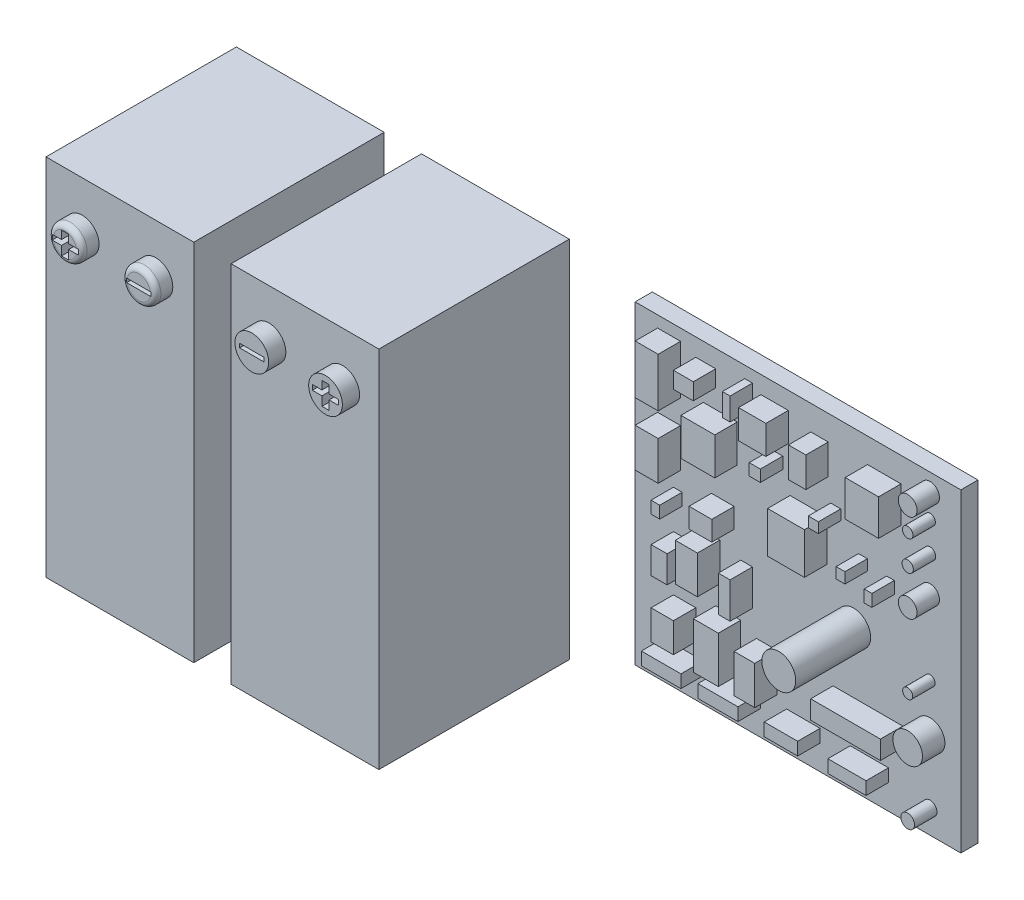
SolidWorks part; units mm, degrees
ref_plane "Front Plane" through (0, 0, 0) normal (0, 0, 1) x (1, 0, 0)
ref_plane "Top Plane" through (0, 0, 0) normal (0, 1, 0) x (1, 0, 0)
ref_plane "Right Plane" through (0, 0, 0) normal (1, 0, 0) x (0, 0, -1)
sketch "Sketch1" plane through (0, 0, 0) normal (0, 0, 1) x (1, 0, 0)
  line L0 (0, 0) -> (-440.234, 0) construction
  line L1 (-308.8617, 138.7667) -> (-252.5588, 138.7667)
  line L2 (-308.8617, 138.7667) -> (-308.8617, 0)
  line L3 (-308.8617, 0) -> (-252.5588, 0)
  line L4 (-252.5588, 138.7667) -> (-252.5588, 0)
  line L5 (-238.3409, 138.7667) -> (-182.0381, 138.7667)
  line L6 (-238.3409, 138.7667) -> (-238.3409, 0)
  line L7 (-238.3409, 0) -> (-182.0381, 0)
  line L8 (-182.0381, 138.7667) -> (-182.0381, 0)
  dimension "D1" = 182.0381
  dimension "D2" = 238.3409
  dimension "D3" = 252.5588
  dimension "D4" = 138.7667
extrude "Boss-Extrude1" add sketch "Sketch1" along normal blind 72.54
sketch "Sketch2" plane through (0, 0, 72.54) normal (0, 0, 1) x (1, 0, 0)
  line L1 (-296.4204, 124.1037) -> (-293.7159, 124.1037)
  line L2 (-296.4204, 124.1037) -> (-296.4204, 120.9679)
  line L3 (-296.4204, 115.561) -> (-293.7159, 115.561)
  line L4 (-293.7159, 124.1037) -> (-293.7159, 120.9679)
  line L5 (-299.9672, 120.9679) -> (-296.4204, 120.9679)
  line L6 (-299.9672, 120.9679) -> (-299.9672, 119.0321)
  line L7 (-299.9672, 119.0321) -> (-296.4204, 119.0321)
  line L8 (-290.0552, 120.9679) -> (-290.0552, 119.0321)
  line L9 (-271.5851, 120.6951) -> (-262.3839, 120.6951)
  line L10 (-271.5851, 120.6951) -> (-271.5851, 119.1782)
  line L11 (-271.5851, 119.1782) -> (-262.3839, 119.1782)
  line L12 (-262.3839, 120.6951) -> (-262.3839, 119.1782)
  line L28 (-293.7159, 119.0321) -> (-290.0552, 119.0321)
  line L29 (-296.4204, 119.0321) -> (-296.4204, 115.561)
  line L30 (-293.7159, 120.9679) -> (-290.0552, 120.9679)
  line L31 (-293.7159, 119.0321) -> (-293.7159, 115.561)
  line L32 (75.3138, 0) -> (-389.5943, 0) construction
  line L33 (-373.4137, 120) -> (67.9111, 120) construction
  line L34 (-308.8617, 138.7667) -> (-308.8617, 0) construction
  line L35 (-295.0748, 110.7152) -> (-295.0748, 129.2848) construction
  line L36 (-308.8617, 0) -> (-252.5588, 0) construction
  line L37 (-304.6062, 120) -> (-285.5434, 120) construction
  line L38 (-266.9845, 132.8771) -> (-266.9845, 104.478) construction
  line L40 (-238.3409, 138.7667) -> (-252.5588, 138.7667) construction
  line L42 (-245.4499, 138.7667) -> (-245.4499, -65.5199) construction
  line L43 (-223.9153, 132.8771) -> (-223.9153, 104.478) construction
  line L44 (-186.2936, 120) -> (-205.3564, 120) construction
  line L45 (-195.825, 110.7152) -> (-195.825, 129.2848) construction
  line L46 (-117.486, 120) -> (-558.8109, 120) construction
  line L47 (-197.1839, 119.0321) -> (-197.1839, 115.561)
  line L48 (-197.1839, 120.9679) -> (-200.8445, 120.9679)
  line L49 (-194.4793, 119.0321) -> (-194.4793, 115.561)
  line L50 (-197.1839, 119.0321) -> (-200.8445, 119.0321)
  line L51 (-228.5159, 120.6951) -> (-228.5159, 119.1782)
  line L52 (-219.3147, 119.1782) -> (-228.5159, 119.1782)
  line L53 (-219.3147, 120.6951) -> (-219.3147, 119.1782)
  line L54 (-219.3147, 120.6951) -> (-228.5159, 120.6951)
  line L55 (-200.8445, 120.9679) -> (-200.8445, 119.0321)
  line L56 (-190.9326, 119.0321) -> (-194.4793, 119.0321)
  line L57 (-190.9326, 120.9679) -> (-190.9326, 119.0321)
  line L58 (-190.9326, 120.9679) -> (-194.4793, 120.9679)
  line L59 (-197.1839, 124.1037) -> (-197.1839, 120.9679)
  line L60 (-194.4793, 115.561) -> (-197.1839, 115.561)
  line L61 (-194.4793, 124.1037) -> (-194.4793, 120.9679)
  line L62 (-194.4793, 124.1037) -> (-197.1839, 124.1037)
  circle A0 centre (-295.0748, 120) radius 6.4293
  circle A1 centre (-266.9845, 120) radius 6.4293
  circle A4 centre (-223.9153, 120) radius 6.4293
  circle A5 centre (-195.825, 120) radius 6.4293
  point P45 (-290.0552, 120)
  point P46 (-295.0748, 120)
  point P57 (-266.9845, 119.1782)
  dimension "D2" = 12.8585
  dimension "D1" = 120
  dimension "D3" = 8.8945
  dimension "D4" = 12.4413
  dimension "D5" = 13.7869
  dimension "D6" = 15.1458
  dimension "D7" = 18.8065
  dimension "D8" = 37.2766
  dimension "D9" = 41.8772
  dimension "D10" = 115.561
  dimension "D11" = 119.0321
  dimension "D12" = 119.1782
  dimension "D13" = 120.6951
  dimension "D15" = 124.1037
extrude "Boss-Extrude2" add sketch "Sketch2" along normal blind 6.54
fillet "Fillet2" radius 2 2 edges at (-288.6455, 120, 79.08) (-260.5552, 120, 79.08)
sketch "Sketch3" plane through (0, 0, 0) normal (0, 0, 1) x (1, 0, 0)
  line L2 (-150.4028, 137.1655) -> (-26.31, 137.1655)
  line L3 (-150.4028, 137.1655) -> (-150.4028, 17.3329)
  line L4 (-150.4028, 17.3329) -> (-26.31, 17.3329)
  line L5 (-26.31, 137.1655) -> (-26.31, 17.3329)
extrude "Boss-Extrude3" add sketch "Sketch3" along normal blind 6.54 separate body
sketch "Sketch4" plane through (0, 0, 6.54) normal (0, 0, 1) x (1, 0, 0)
  line L0 (-124.4242, 116.9736) -> (-111.5093, 116.9736)
  line L29 (-124.4242, 116.9736) -> (-124.4242, 102.7654)
  line L30 (-124.4242, 102.7654) -> (-111.5093, 102.7654)
  line L31 (-111.5093, 116.9736) -> (-111.5093, 102.7654)
  line L32 (-61.8527, 127.7413) -> (-49.1154, 127.7413)
  line L33 (-61.8527, 127.7413) -> (-61.8527, 114.0263)
  line L34 (-61.8527, 114.0263) -> (-49.1154, 114.0263)
  line L35 (-49.1154, 127.7413) -> (-49.1154, 114.0263)
  line L36 (-91.3846, 102.7654) -> (-77.364, 102.7654)
  line L37 (-91.3846, 102.7654) -> (-91.3846, 87.0185)
  line L38 (-91.3846, 87.0185) -> (-77.364, 87.0185)
  line L39 (-77.364, 102.7654) -> (-77.364, 87.0185)
  line L40 (-139.4923, 31.6753) -> (-124.4242, 31.6753)
  line L41 (-139.4923, 31.6753) -> (-139.4923, 26.7954)
  line L42 (-139.4923, 26.7954) -> (-124.4242, 26.7954)
  line L43 (-124.4242, 31.6753) -> (-124.4242, 26.7954)
  line L44 (-117.9667, 26.7954) -> (-102.6774, 26.7954)
  line L45 (-117.9667, 26.7954) -> (-117.9667, 31.6753)
  line L46 (-117.9667, 31.6753) -> (-102.6774, 31.6753)
  line L47 (-102.6774, 26.7954) -> (-102.6774, 31.6753)
  line L48 (-92.6889, 26.7954) -> (-79.9401, 26.7954)
  line L49 (-92.6889, 26.7954) -> (-92.6889, 31.6753)
  line L50 (-92.6889, 31.6753) -> (-79.9401, 31.6753)
  line L51 (-79.9401, 26.7954) -> (-79.9401, 31.6753)
  line L52 (-68.4298, 26.7954) -> (-53.88, 26.7954)
  line L53 (-68.4298, 26.7954) -> (-68.4298, 31.6753)
  line L54 (-68.4298, 31.6753) -> (-53.88, 31.6753)
  line L55 (-53.88, 26.7954) -> (-53.88, 31.6753)
extrude "Boss-Extrude4" add sketch "Sketch4" along normal blind 8.54
sketch "Sketch5" plane through (0, 0, 6.54) normal (0, 0, 1) x (1, 0, 0)
  line L1 (-126.5753, 74.6743) -> (-118.1553, 74.6743)
  line L2 (-126.5753, 74.6743) -> (-126.5753, 60.2183)
  line L3 (-126.5753, 60.2183) -> (-118.1553, 60.2183)
  line L4 (-118.1553, 74.6743) -> (-118.1553, 60.2183)
  line L5 (-83.4596, 127.7011) -> (-76.8359, 127.7011)
  line L6 (-83.4596, 127.7011) -> (-83.4596, 116.242)
  line L7 (-83.4596, 116.242) -> (-76.8359, 116.242)
  line L8 (-76.8359, 127.7011) -> (-76.8359, 116.242)
  line L9 (-141.8562, 132.7867) -> (-133.098, 132.7867)
  line L10 (-141.8562, 132.7867) -> (-141.8562, 114.0969)
  line L11 (-141.8562, 114.0969) -> (-133.098, 114.0969)
  line L12 (-133.098, 132.7867) -> (-133.098, 114.0969)
  line L13 (-141.8562, 104.9894) -> (-133.098, 104.9894)
  line L14 (-141.8562, 104.9894) -> (-141.8562, 90.1928)
  line L15 (-141.8562, 90.1928) -> (-133.098, 90.1928)
  line L16 (-133.098, 104.9894) -> (-133.098, 90.1928)
  line L17 (-102.4628, 130.5106) -> (-92.0529, 130.5106)
  line L18 (-102.4628, 130.5106) -> (-102.4628, 119.5635)
  line L19 (-102.4628, 119.5635) -> (-92.0529, 119.5635)
  line L20 (-92.0529, 130.5106) -> (-92.0529, 119.5635)
  circle A0 centre (-38.0241, 130.5106) radius 3.5787
  circle A1 centre (-38.0241, 121.5725) radius 2.009
  circle A2 centre (-38.0241, 110.3479) radius 2.1496
  circle A3 centre (-38.0241, 96.8075) radius 3.5608
  circle A4 centre (-38.0241, 68.4245) radius 1.918
  circle A5 centre (-38.0241, 50.4978) radius 5.6384
  circle A6 centre (-38.0241, 26.3267) radius 2.6127
extrude "Boss-Extrude5" add sketch "Sketch5" along normal blind 8.54
sketch "Sketch6" plane through (0, 0, 6.54) normal (0, 0, 1) x (1, 0, 0)
  line L1 (-74.9839, 48.1631) -> (-48.4162, 48.1631)
  line L2 (-74.9839, 48.1631) -> (-74.9839, 41.0683)
  line L3 (-74.9839, 41.0683) -> (-48.4162, 41.0683)
  line L4 (-48.4162, 48.1631) -> (-48.4162, 41.0683)
  circle A0 centre (-86.3419, 53.3223) radius 2.8881
extrude "Boss-Extrude6" add sketch "Sketch6" along normal blind 8.54
sketch "Sketch7" plane through (0, 0, 6.54) normal (0, 0, 1) x (1, 0, 0)
  line L1 (-65.2782, 96.6536) -> (-61.9213, 96.6536)
  line L2 (-65.2782, 96.6536) -> (-65.2782, 92.5498)
  line L3 (-65.2782, 92.5498) -> (-61.9213, 92.5498)
  line L4 (-61.9213, 96.6536) -> (-61.9213, 92.5498)
  line L5 (-54.575, 94.6017) -> (-51.6575, 94.6017)
  line L6 (-54.575, 94.6017) -> (-54.575, 89.9723)
  line L7 (-54.575, 89.9723) -> (-51.6575, 89.9723)
  line L8 (-51.6575, 94.6017) -> (-51.6575, 89.9723)
  line L9 (-75.9021, 108.0229) -> (-72.0603, 108.0229)
  line L10 (-75.9021, 108.0229) -> (-75.9021, 104.1182)
  line L11 (-75.9021, 104.1182) -> (-72.0603, 104.1182)
  line L12 (-72.0603, 108.0229) -> (-72.0603, 104.1182)
  line L13 (-98.4188, 114.3868) -> (-94.1601, 114.3868)
  line L14 (-98.4188, 114.3868) -> (-98.4188, 109.9382)
  line L15 (-98.4188, 109.9382) -> (-94.1601, 109.9382)
  line L16 (-94.1601, 114.3868) -> (-94.1601, 109.9382)
  line L17 (-127.2818, 130.4207) -> (-119.6928, 130.4207)
  line L18 (-127.2818, 130.4207) -> (-127.2818, 124.122)
  line L19 (-127.2818, 124.122) -> (-119.6928, 124.122)
  line L20 (-119.6928, 130.4207) -> (-119.6928, 124.122)
  line L21 (-108.6375, 132.7168) -> (-105.6896, 132.7168)
  line L22 (-108.6375, 132.7168) -> (-108.6375, 124.122)
  line L23 (-108.6375, 124.122) -> (-105.6896, 124.122)
  line L24 (-105.6896, 132.7168) -> (-105.6896, 124.122)
  line L25 (-135.805, 83.2928) -> (-132.4936, 83.2928)
  line L26 (-135.805, 83.2928) -> (-135.805, 78.6934)
  line L27 (-135.805, 78.6934) -> (-132.4936, 78.6934)
  line L28 (-132.4936, 83.2928) -> (-132.4936, 78.6934)
  line L29 (-121.3247, 88.5268) -> (-112.671, 88.5268)
  line L30 (-121.3247, 88.5268) -> (-121.3247, 80.9931)
  line L31 (-121.3247, 80.9931) -> (-112.671, 80.9931)
  line L32 (-112.671, 88.5268) -> (-112.671, 80.9931)
  line L33 (-135.805, 68.6524) -> (-129.6893, 68.6524)
  line L34 (-135.805, 68.6524) -> (-135.805, 58.3901)
  line L35 (-135.805, 58.3901) -> (-129.6893, 58.3901)
  line L36 (-129.6893, 68.6524) -> (-129.6893, 58.3901)
  line L37 (-135.805, 47.7756) -> (-127.2818, 47.7756)
  line L38 (-135.805, 47.7756) -> (-135.805, 36.5276)
  line L39 (-135.805, 36.5276) -> (-127.2818, 36.5276)
  line L40 (-127.2818, 47.7756) -> (-127.2818, 36.5276)
  line L41 (-119.6928, 52.2232) -> (-110.1728, 52.2232)
  line L42 (-119.6928, 52.2232) -> (-119.6928, 34.5827)
  line L43 (-119.6928, 34.5827) -> (-110.1728, 34.5827)
  line L44 (-110.1728, 52.2232) -> (-110.1728, 34.5827)
  line L45 (-110.1728, 72.0575) -> (-105.6896, 72.0575)
  line L46 (-110.1728, 72.0575) -> (-110.1728, 58.3901)
  line L47 (-110.1728, 58.3901) -> (-105.6896, 58.3901)
  line L48 (-105.6896, 72.0575) -> (-105.6896, 58.3901)
  line L49 (-104.1643, 49.2094) -> (-96.2894, 49.2094)
  line L50 (-104.1643, 49.2094) -> (-104.1643, 34.5827)
  line L51 (-104.1643, 34.5827) -> (-96.2894, 34.5827)
  line L52 (-96.2894, 49.2094) -> (-96.2894, 34.5827)
extrude "Boss-Extrude7" add sketch "Sketch7" along normal blind 8.54
sketch "Sketch8" plane through (0, 0, 6.54) normal (0, 0, 1) x (1, 0, 0)
  circle A0 centre (-67.1281, 71.2808) radius 6.4605
extrude "Boss-Extrude8" add sketch "Sketch8" along normal blind 28.54
